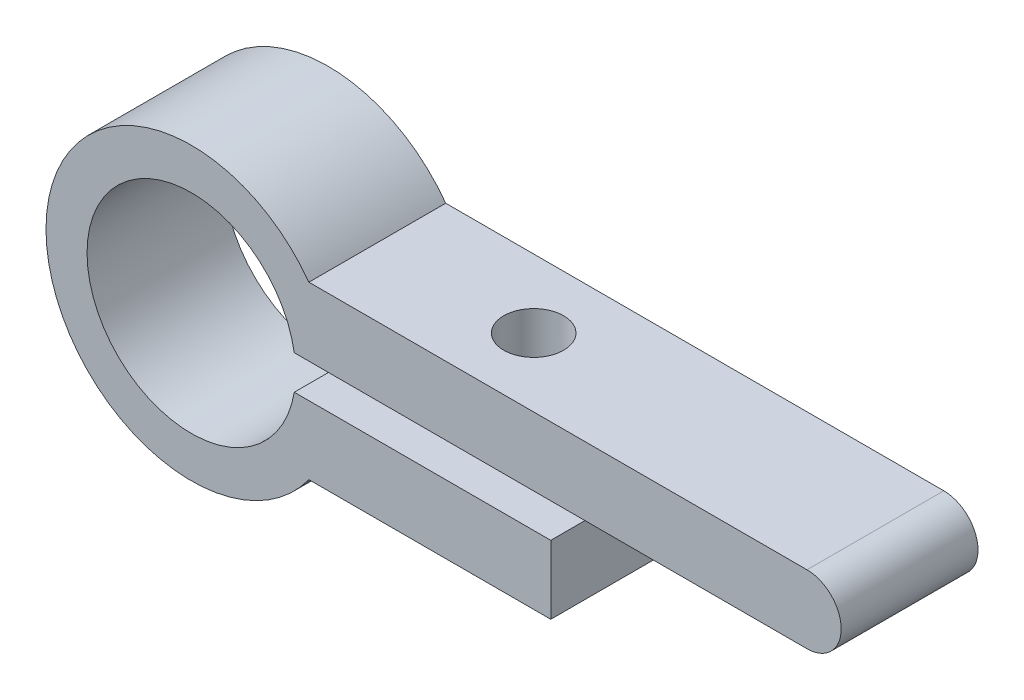
SolidWorks part; units mm, degrees
ref_plane "Plano frontal" through (0, 0, 0) normal (0, 0, 1) x (1, 0, 0)
ref_plane "Plano superior" through (0, 0, 0) normal (0, 1, 0) x (1, 0, 0)
ref_plane "Plano direito" through (0, 0, 0) normal (1, 0, 0) x (0, 0, -1)
sketch "Esboço1" plane through (0, 0, 0) normal (0, 0, 1) x (1, 0, 0)
  line L1 (6.0175, 1) -> (8.441, 1)
  line L3 (6.0175, -1) -> (8.441, -1)
  arc A0 (6.0175, 1) -> (6.0175, -1) centre (0, 0) ccw
  arc A1 (8.441, 1) -> (8.441, -1) centre (0, 0) ccw
  dimension "D1" = 12.2
  dimension "D2" = 17
  dimension "D3" = 1
  dimension "D4" = 1
extrude "Ressalto-extrusão1" add sketch "Esboço1" along normal blind 8
sketch "Esboço2" plane through (0, 0, 8) normal (0, 0, 1) x (1, 0, 0)
  line L1 (6.0175, 1) -> (36, 1)
  line L2 (6.0175, 1) -> (6.0175, 5)
  line L3 (6.0175, 5) -> (36, 5)
  line L5 (6.0175, -1) -> (21.0175, -1)
  line L6 (6.0175, -1) -> (6.0175, -5)
  line L7 (6.0175, -5) -> (21.0175, -5)
  line L8 (21.0175, -1) -> (21.0175, -5)
  arc A0 (36, 1) -> (36, 5) centre (36, 3) ccw
  dimension "D3" = 36
  dimension "D5" = 2
  dimension "D1" = 4
  dimension "D2" = 4
  dimension "D4" = 15
extrude "Ressalto-extrusão2" add sketch "Esboço2" against normal through all
sketch "Esboço3" plane through (0, -5, 0) normal (0, -1, 0) x (1, 0, 0)
  line L0 (21.0175, 0) -> (21.0175, 8) construction
  circle A0 centre (16.0175, 4) radius 1.75
  point P4 (21.0175, 4)
  dimension "D1" = 3.5
  dimension "D2" = 5
  dimension "D3" = 0
extrude "Corte-extrusão1" cut sketch "Esboço3" against normal through all
sketch "Esboço4" plane through (0, -5, 0) normal (0, -1, 0) x (1, 0, 0)
  line L0 (6.8739, 8) -> (21.0175, 8) construction
  line L1 (19.597, 4) -> (17.8073, 7.1)
  line L2 (17.8073, 7.1) -> (14.2277, 7.1)
  line L3 (14.2277, 7.1) -> (12.4379, 4)
  line L4 (12.4379, 4) -> (14.2277, 0.9)
  line L5 (14.2277, 0.9) -> (17.8073, 0.9)
  line L6 (17.8073, 0.9) -> (19.597, 4)
  circle A0 centre (16.0175, 4) radius 3.1 construction
  dimension "D1" = 6.2
  dimension "D2" = 0
extrude "Corte-extrusão2" cut sketch "Esboço4" against normal blind 2.5
